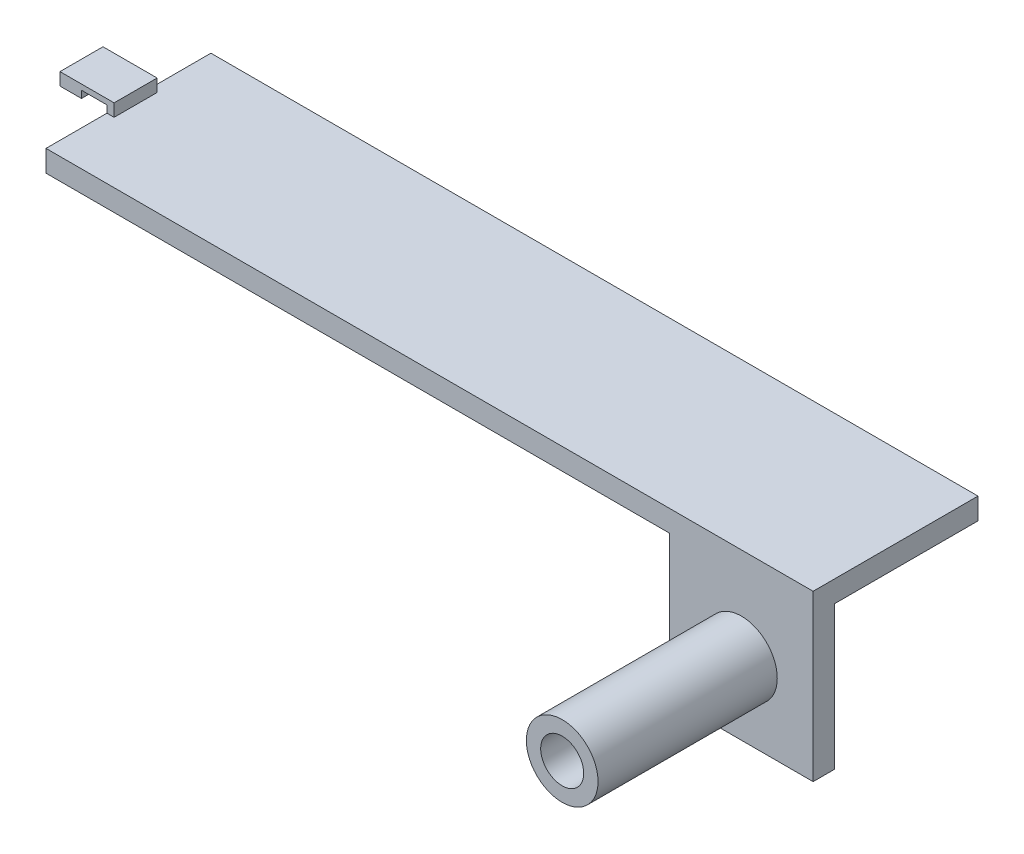
SolidWorks part; units mm, degrees
ref_plane "Front Plane" through (0, 0, 0) normal (0, 0, 1) x (1, 0, 0)
ref_plane "Top Plane" through (0, 0, 0) normal (0, 1, 0) x (1, 0, 0)
ref_plane "Right Plane" through (0, 0, 0) normal (1, 0, 0) x (0, 0, -1)
sketch "Sketch2" plane through (0, 0, 0) normal (1, 0, 0) x (0, 0, -1)
  line L0 (0, 0) -> (-23, 0)
  line L1 (-23, 0) -> (-23, -23)
  line L2 (-23, -23) -> (-20, -23)
  line L3 (-20, -23) -> (-20, -3)
  line L4 (-20, -3) -> (0, -3)
  line L5 (0, -3) -> (0, 0)
  dimension "D1" = 23
  dimension "D2" = 3
  dimension "D3" = 3
  dimension "D4" = 23
extrude "Boss-Extrude1" add sketch "Sketch2" against normal blind 107
sketch "Sketch3" plane through (0, 0, 0) normal (0, 1, 0) x (1, 0, 0)
  line L0 (-107, 0) -> (-107, -23) construction
  line L1 (-107, 0) -> (0, 0) construction
  circle A0 centre (-102.9, -11.5) radius 2.5
  dimension "D1" = 5
  dimension "D2" = 4.1
  dimension "D3" = 11.5
sketch "Sketch7" plane through (0, 0, 23) normal (0, 0, 1) x (1, 0, 0)
  line L0 (-107, 0) -> (-107, -23) construction
  line L1 (-107, -3) -> (-20, -3)
  line L2 (-107, -3) -> (-107, -23)
  line L3 (-107, -23) -> (-20, -23)
  line L4 (-20, -3) -> (-20, -23)
  line L5 (-107, -23) -> (0, -23) construction
  dimension "D1" = 87
  dimension "D2" = 20
extrude "Cut-Extrude4" cut sketch "Sketch7" against normal blind 25
sketch "Sketch8" plane through (0, 0, 23) normal (0, 0, 1) x (1, 0, 0)
  line L0 (0, 0) -> (0, -23) construction
  line L1 (-20, -23) -> (0, -23) construction
  circle A0 centre (-10, -13) radius 5
  circle A1 centre (-10, -13) radius 3
  dimension "D1" = 10
  dimension "D4" = 6
  dimension "D2" = 10
  dimension "D3" = 10
extrude "Boss-Extrude3" add sketch "Sketch8" along normal blind 25
sketch "Sketch9" plane through (0, 0, 0) normal (0, 0, 1) x (1, 0, 0)
  line L0 (-107, 0) -> (-107, 1)
  line L1 (-106.7824, 0) -> (-106.7824, 1) construction
  line L2 (-110.55, 1.75) -> (-113.55, 1.75)
  line L3 (-106, 1.75) -> (-106, 0)
  line L4 (-106.7824, 1) -> (-107, 1) construction
  line L5 (-113.55, 1.75) -> (-113.55, 0)
  line L6 (-110.55, 1) -> (-110.55, 0)
  line L7 (-110.55, 1.75) -> (-106, 1.75)
  line L8 (-110.55, 1) -> (-107, 1)
  line L9 (-110.55, 0) -> (-113.55, 0)
  line L10 (-107, 0) -> (-106, 0)
  point P11 (0, 0)
  point P12 (0, 0)
  point P13 (-109.4401, 3.0847)
  point P14 (-107, 0)
  dimension "D1" = 1
  dimension "D2" = 3.55
  dimension "D3" = 3
  dimension "D4" = 1
  dimension "D5" = 0.75
  dimension "D6" = 1.75
extrude "Boss-Extrude4" add sketch "Sketch9" along normal blind 3 and the other way blind 3 from vertex starting at point (-102.9, 0, 11.5)
